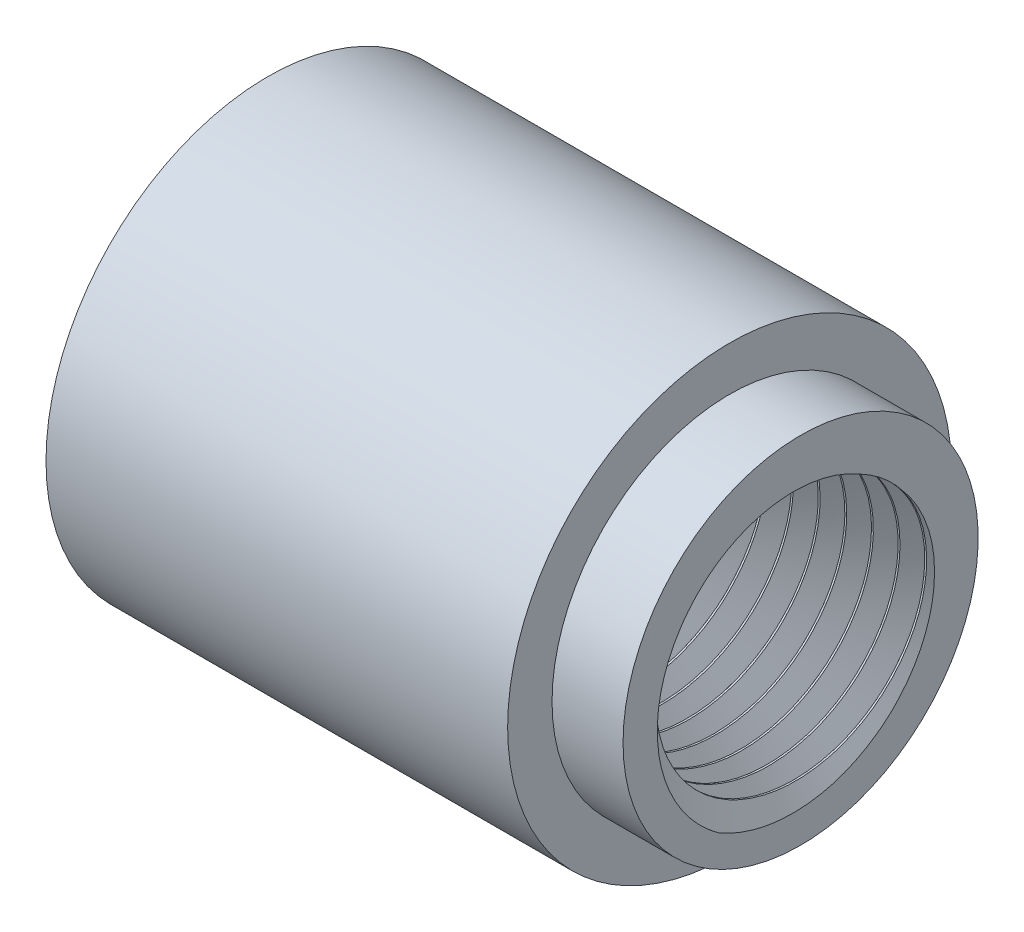
SolidWorks part; units mm, degrees
ref_plane "Alzado" through (0, 0, 0) normal (0, 0, 1) x (1, 0, 0)
ref_plane "Planta" through (0, 0, 0) normal (0, 1, 0) x (1, 0, 0)
ref_plane "Vista lateral" through (0, 0, 0) normal (1, 0, 0) x (0, 0, -1)
sketch "Croquis1" plane through (0, 0, 0) normal (0, 0, 1) x (1, 0, 0)
  line L0 (0, 0) -> (34.5991, 0) construction
  line L1 (0, 7.25) -> (30, 7.25)
  line L2 (30, 7.25) -> (30, 10)
  line L3 (30, 10) -> (26, 10)
  line L4 (26, 10) -> (26, 12.5)
  line L5 (26, 12.5) -> (0, 12.5)
  line L6 (0, 12.5) -> (0, 7.25)
  dimension "D1" = 14.5
  dimension "D2" = 26
  dimension "D3" = 4
  dimension "D4" = 25
  dimension "D5" = 2.5
revolve "Revolución1" add sketch "Croquis1" angle 360 about L0
sketch "Croquis2" plane through (30, 0, 0) normal (1, 0, 0) x (0, 0, -1)
  circle A0 centre (0, 0) radius 7.25 construction
  circle A1 centre (0, 0) radius 7.25
curve "Hélice/Espiral1" pitch 1.5 height 39 turns 26
ref_plane "Plano1" through (-9, 5.1265, -5.1265) normal (-0.0329, -0.7067, -0.7067) x (-0.9995, 0.0233, 0.0233)
sketch "Croquis3" plane through (-9, 5.1265, -5.1265) normal (-0.0329, -0.7067, -0.7067) x (-0.9995, 0.0233, 0.0233)
  line L0 (-1.4363, -0.0176) -> (-0.0222, -0.0176)
  line L1 (-0.0222, -0.0176) -> (-0.6997, 1.2065)
  line L2 (-0.6997, 1.2065) -> (-1.4363, -0.0176)
  dimension "D1" = 60
sweep "Cortar-Barrer2" cut profiles "Croquis3" path "Hélice/Espiral1"
